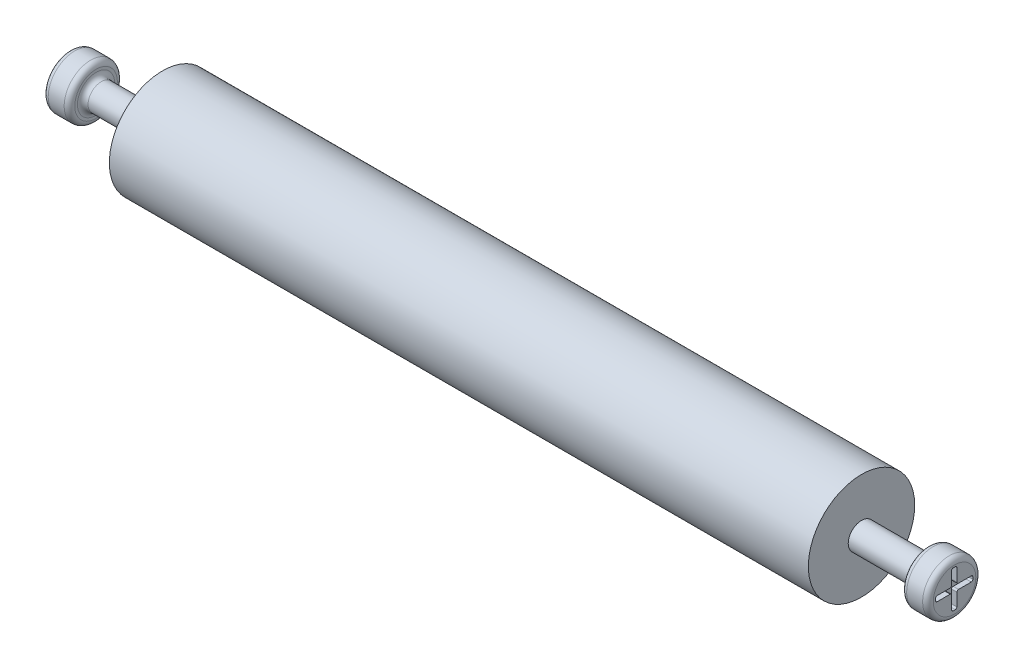
SolidWorks part; units mm, degrees
ref_plane "Front Plane" through (0, 0, 0) normal (0, 0, 1) x (1, 0, 0)
ref_plane "Top Plane" through (0, 0, 0) normal (0, 1, 0) x (1, 0, 0)
ref_plane "Right Plane" through (0, 0, 0) normal (1, 0, 0) x (0, 0, -1)
sketch "Sketch1" plane through (0, 0, 0) normal (1, 0, 0) x (0, 0, -1)
  circle A0 centre (0, 0) radius 25.4
extrude "Boss-Extrude1" add sketch "Sketch1" along normal blind 167.005 and the other way blind 167.005
sketch "Sketch2" plane through (-167.005, 0, 0) normal (-1, 0, 0) x (0, 0, 1)
  circle A0 centre (0, 0) radius 6.35
extrude "Boss-Extrude2" add sketch "Sketch2" along normal blind 31.75
sketch "Sketch3" plane through (-198.755, 0, 0) normal (-1, 0, 0) x (0, 0, 1)
  circle A0 centre (0, 0) radius 12.7
extrude "Boss-Extrude3" add sketch "Sketch3" along normal blind 12.7
fillet "Fillet2" radius 2.54 3 edges at (-198.755, 0, 6.35) (-198.755, 0, 12.7) (-211.455, 0, 12.7)
sketch "Sketch4" plane through (-211.455, 0, 0) normal (-1, 0, 0) x (0, 0, 1)
  line L0 (-0.3597, 9.2606) -> (0.6563, 9.2606)
  line L1 (-1.1217, 8.4986) -> (-1.1217, 2.4026)
  line L2 (-0.3597, -8.5194) -> (0.6563, -8.5194)
  line L3 (1.4183, 8.4986) -> (1.4183, 2.4026)
  line L4 (-7.9797, 1.6406) -> (-1.8837, 1.6406)
  line L5 (-8.7417, 0.8786) -> (-8.7417, -0.1374)
  line L6 (-7.9797, -0.8994) -> (-1.8837, -0.8994)
  line L7 (9.0383, 0.8786) -> (9.0383, -0.1374)
  line L8 (1.4183, -1.6614) -> (1.4183, -7.7574)
  line L9 (-1.1217, -1.6614) -> (-1.1217, -7.7574)
  line L10 (2.1803, -0.8994) -> (8.2763, -0.8994)
  line L11 (2.1803, 1.6406) -> (8.2763, 1.6406)
  arc A0 (-8.7417, -0.1374) -> (-7.9797, -0.8994) centre (-7.9797, -0.1374) ccw
  arc A1 (-1.1217, -1.6614) -> (-1.8837, -0.8994) centre (-1.8837, -1.6614) ccw
  arc A2 (1.4183, -1.6614) -> (2.1803, -0.8994) centre (2.1803, -1.6614) cw
  arc A3 (-0.3597, -8.5194) -> (-1.1217, -7.7574) centre (-0.3597, -7.7574) cw
  arc A4 (0.6563, -8.5194) -> (1.4183, -7.7574) centre (0.6563, -7.7574) ccw
  arc A5 (9.0383, 0.8786) -> (8.2763, 1.6406) centre (8.2763, 0.8786) ccw
  arc A6 (9.0383, -0.1374) -> (8.2763, -0.8994) centre (8.2763, -0.1374) cw
  arc A7 (-1.1217, 8.4986) -> (-0.3597, 9.2606) centre (-0.3597, 8.4986) cw
  arc A8 (-8.7417, 0.8786) -> (-7.9797, 1.6406) centre (-7.9797, 0.8786) cw
  arc A9 (1.4183, 8.4986) -> (0.6563, 9.2606) centre (0.6563, 8.4986) ccw
  arc A10 (2.1803, 1.6406) -> (1.4183, 2.4026) centre (2.1803, 2.4026) cw
  arc A11 (-1.1217, 2.4026) -> (-1.8837, 1.6406) centre (-1.8837, 2.4026) cw
  point P0 (0.1483, 0.3706)
  point P5 (0.1483, 0.3706)
  dimension "D1" = 0.762
  dimension "D2" = 0.762
  dimension "D3" = 0.762
extrude "Cut-Extrude1" cut sketch "Sketch4" against normal blind 2.54
mirror "Mirror1" about plane through (0, 0, 0) normal (1, 0, 0) of "Boss-Extrude2", "Cut-Extrude1", "Fillet2", "Boss-Extrude3"
